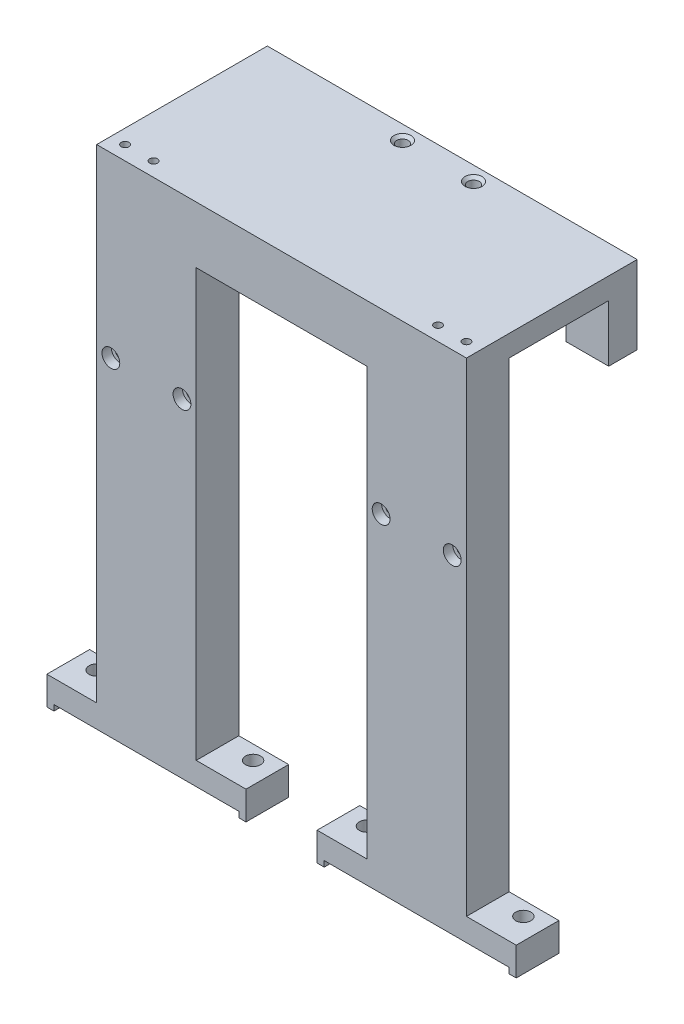
SolidWorks part; units mm, degrees
material "6061 Alloy"
ref_plane "Front Plane" through (0, 0, 0) normal (0, 0, 1) x (1, 0, 0)
ref_plane "Top Plane" through (0, 0, 0) normal (0, 1, 0) x (1, 0, 0)
ref_plane "Right Plane" through (0, 0, 0) normal (1, 0, 0) x (0, 0, -1)
sketch "Sketch1" plane through (0, 0, 0) normal (0, 0, 1) x (1, 0, 0)
  line L1 (-82.55, -114.3) -> (82.55, -114.3)
  line L2 (-82.55, -114.3) -> (-82.55, 114.3)
  line L3 (-82.55, 114.3) -> (82.55, 114.3)
  line L4 (82.55, -114.3) -> (82.55, 114.3)
  line L5 (-82.55, -114.3) -> (82.55, 114.3) construction
  line L6 (-82.55, 114.3) -> (82.55, -114.3) construction
  point P0 (0, 0)
  dimension "D1" = 228.6
  dimension "D2" = 165.1
extrude "Boss-Extrude1" add sketch "Sketch1" along normal blind 19.05
sketch "Sketch2" plane through (0, 0, 19.05) normal (0, 0, 1) x (1, 0, 0)
  line L0 (-82.55, -114.3) -> (82.55, -114.3) construction
  line L1 (-38.1, -114.3) -> (38.1, -114.3)
  line L2 (-38.1, -114.3) -> (-38.1, 88.9)
  line L3 (-38.1, 88.9) -> (38.1, 88.9)
  line L4 (38.1, -114.3) -> (38.1, 88.9)
  line L5 (-82.55, 114.3) -> (-82.55, -114.3) construction
  dimension "D1" = 203.2
  dimension "D2" = 76.2
  dimension "D3" = 44.45
extrude "Cut-Extrude1" cut sketch "Sketch2" against normal through all
sketch "Sketch3" plane through (0, 0, 0) normal (0, 0, -1) x (-1, 0, 0)
  line L0 (82.55, 114.3) -> (82.55, -114.3) construction
  line L1 (-82.55, 114.3) -> (82.55, 114.3)
  line L2 (-82.55, 114.3) -> (-82.55, 104.775)
  line L3 (-82.55, 104.775) -> (82.55, 104.775)
  line L4 (82.55, 114.3) -> (82.55, 104.775)
  dimension "D1" = 9.525
extrude "Boss-Extrude2" add sketch "Sketch3" along normal blind 57.15
sketch "Sketch4" plane through (0, 0, -57.15) normal (0, 0, -1) x (-1, 0, 0)
  line L7 (-82.55, 104.775) -> (-63.5, 104.775)
  line L8 (-82.55, 104.775) -> (-82.55, 79.375)
  line L9 (-82.55, 79.375) -> (-63.5, 79.375)
  line L10 (-63.5, 104.775) -> (-63.5, 79.375)
  dimension "D1" = 25.4
  dimension "D2" = 19.05
extrude "Boss-Extrude3" add sketch "Sketch4" against normal blind 12.7
mirror "Mirror1" about plane through (0, 0, 0) normal (1, 0, 0) of "Boss-Extrude3"
sketch "Sketch7" plane through (0, 0, 19.05) normal (0, 0, 1) x (1, 0, 0)
  line L0 (-82.55, -114.3) -> (-38.1, -114.3) construction
  line L1 (-104.775, -101.6) -> (-15.875, -101.6)
  line L2 (-104.775, -101.6) -> (-104.775, -114.3)
  line L3 (-104.775, -114.3) -> (-15.875, -114.3)
  line L4 (-15.875, -101.6) -> (-15.875, -114.3)
  line L5 (-104.775, -101.6) -> (-15.875, -114.3) construction
  line L6 (-104.775, -114.3) -> (-15.875, -101.6) construction
  line L7 (-82.55, 114.3) -> (-82.55, -114.3) construction
  point P0 (-60.325, -107.95)
  dimension "D1" = 0
  dimension "D2" = 88.9
  dimension "D3" = 22.225
  dimension "D4" = 12.7
extrude "Boss-Extrude4" add sketch "Sketch7" against normal blind 19.05
sketch "Sketch8" plane through (0, -114.3, 0) normal (0, -1, 0) x (-1, 0, 0)
  line L0 (104.775, -19.05) -> (15.875, -19.05) construction
  line L1 (101.6, 0) -> (19.05, 0)
  line L2 (101.6, 0) -> (101.6, -19.05)
  line L3 (101.6, -19.05) -> (19.05, -19.05)
  line L4 (19.05, 0) -> (19.05, -19.05)
  line L5 (101.6, 0) -> (19.05, -19.05) construction
  line L6 (101.6, -19.05) -> (19.05, 0) construction
  line L8 (104.775, 0) -> (104.775, -19.05) construction
  line L9 (15.875, 0) -> (15.875, -19.05) construction
  point P0 (60.325, -9.525)
  dimension "D1" = 19.05
  dimension "D2" = 3.175
  dimension "D3" = 3.175
extrude "Cut-Extrude4" cut sketch "Sketch8" against normal blind 2.54
mirror "Mirror3" about plane through (0, 0, 0) normal (1, 0, 0) of "Cut-Extrude4", "Boss-Extrude4"
hole_wizard "#8-32 Tapped Hole1" positions "Sketch11" profile "Sketch10" tap size "#8-32" standard "ANSI Inch"
sketch "Sketch11" plane through (0, 114.3, 0) normal (0, 1, 0) x (1, 0, 0)
  line L0 (-82.55, 0) -> (-82.55, -19.05) construction
  line L1 (-82.55, -19.05) -> (-82.55, 57.15) construction
  line L2 (82.55, 0) -> (82.55, -19.05) construction
  line L3 (82.55, -19.05) -> (82.55, 57.15) construction
  line L4 (82.55, -19.05) -> (-82.55, -19.05) construction
  point P0 (-76.2, -12.7)
  point P2 (-63.5, -12.7)
  point P4 (63.5, -12.7)
  point P6 (76.2, -12.7)
  dimension "D1" = 6.35
  dimension "D2" = 19.05
  dimension "D3" = 6.35
  dimension "D4" = 19.05
  dimension "D5" = 6.35
  dimension "D6" = 6.35
  dimension "D7" = 6.35
  dimension "D8" = 6.35
cosmetic thread "Hole Thread1" parameters "D1"=3.048, "D2"=4.1656
cosmetic thread "Hole Thread2" parameters "D1"=3.048, "D2"=4.1656
cosmetic thread "Hole Thread3" parameters "D1"=3.048, "D2"=4.1656
cosmetic thread "Hole Thread4" parameters "D1"=3.048, "D2"=4.1656
sketch "Sketch10" plane through (-76.2, 114.3, 12.7) normal (1, 0, 0) x (0, 0, 1)
  line L0 (0, 0) -> (0, 13.7378)
  line L1 (0, 13.7378) -> (1.7272, 12.7)
  line L2 (1.7272, 12.7) -> (1.7272, 0)
  line L5 (1.7272, 0) -> (0, 0)
  line L10 (0, 13.7378) -> (-1.7272, 12.7) construction
  line L11 (0, -6.35) -> (0, 107.95) construction
  dimension "Tap Drill Dia." = 3.4544
  dimension "Tap Drill Depth" = 12.7
  dimension "Drill Angle" = 118
hole_wizard "1/4 Clearance Hole1" positions "Sketch12" profile "Sketch13" hole size "1/4" standard "ANSI Inch" end condition up to next
sketch "Sketch12" plane through (0, -101.6, 0) normal (0, 1, 0) x (1, 0, 0)
  line L0 (-104.775, 0) -> (-104.775, -19.05) construction
  line L1 (-82.55, 0) -> (-104.775, 0) construction
  line L2 (-15.875, 0) -> (-38.1, 0) construction
  line L3 (-15.875, 0) -> (-15.875, -19.05) construction
  line L4 (15.875, 0) -> (15.875, -19.05) construction
  line L5 (15.875, 0) -> (38.1, 0) construction
  line L6 (82.55, 0) -> (104.775, 0) construction
  line L7 (104.775, 0) -> (104.775, -19.05) construction
  point P0 (-95.25, -6.35)
  point P2 (-25.4, -6.35)
  point P4 (25.4, -6.35)
  point P6 (95.25, -6.35)
  dimension "D1" = 9.525
  dimension "D2" = 6.35
  dimension "D3" = 6.35
  dimension "D4" = 9.525
  dimension "D5" = 9.525
  dimension "D6" = 6.35
  dimension "D7" = 6.35
  dimension "D8" = 9.525
sketch "Sketch13" plane through (-95.25, -101.6, 6.35) normal (1, 0, 0) x (0, 0, 1)
  line L0 (0, 0) -> (0, 10.16)
  line L1 (0, 10.16) -> (3.3782, 10.16)
  line L2 (3.3782, 10.16) -> (3.3782, 0)
  line L5 (3.3782, 0) -> (0, 0)
  line L11 (0, -6.35) -> (0, 107.95) construction
  dimension "Thru Hole Dia." = 6.7564
  dimension "Thru Hole Depth" = 10.16
hole_wizard "CBORE for #8 Socket Head Cap Screw1" positions "Sketch18" profile "Sketch19" counterbore size "#8" standard "ANSI Inch" end condition up to next
sketch "Sketch18" plane through (0, 0, 19.05) normal (0, 0, 1) x (1, 0, 0)
  line L0 (-82.55, 114.3) -> (-82.55, -101.6) construction
  line L1 (-38.1, 88.9) -> (-38.1, -101.6) construction
  line L2 (38.1, -101.6) -> (38.1, 88.9) construction
  line L3 (82.55, -101.6) -> (82.55, 114.3) construction
  point P0 (-76.2, 34.925)
  point P2 (-44.45, 34.925)
  point P4 (44.45, 34.925)
  point P6 (76.2, 34.925)
  dimension "D1" = 6.35
  dimension "D2" = 6.35
  dimension "D3" = 6.35
  dimension "D4" = 6.35
  dimension "D5" = 136.525
  dimension "D6" = 136.525
  dimension "D7" = 136.525
  dimension "D8" = 136.525
sketch "Sketch19" plane through (-76.2, 34.925, 19.05) normal (1, 0, 0) x (0, -1, 0)
  line L0 (0, 0) -> (0, 19.05)
  line L1 (0, 19.05) -> (2.2479, 19.05)
  line L3 (2.2479, 19.05) -> (2.2479, 4.1656)
  line L4 (2.2479, 4.1656) -> (3.9687, 4.1656)
  line L5 (3.9687, 4.1656) -> (3.9687, 0)
  line L7 (3.9687, 0) -> (0, 0)
  line L11 (0, -6.35) -> (0, 107.95) construction
  dimension "Thru Hole Dia." = 4.4958
  dimension "Thru Hole Depth" = 19.05
  dimension "C'Bore Dia." = 7.9375
  dimension "C'Bore Depth" = 4.1656
hole_wizard "1/4-20 Tapped Hole1" positions "Sketch20" profile "Sketch21" tap size "1/4-20" standard "ANSI Inch" end condition through all
sketch "Sketch20" plane through (0, 114.3, 0) normal (0, 1, 0) x (1, 0, 0)
  line L0 (-82.55, -19.05) -> (-82.55, 57.15) construction
  line L1 (82.55, -19.05) -> (82.55, 57.15) construction
  line L2 (-82.55, 57.15) -> (82.55, 57.15) construction
  point P0 (15.875, 50.8)
  point P2 (-15.875, 50.8)
  dimension "D1" = 66.675
  dimension "D2" = 66.675
  dimension "D3" = 6.35
  dimension "D4" = 6.35
sketch "Sketch21" plane through (15.875, 114.3, -50.8) normal (1, 0, 0) x (0, 0, 1)
  line L0 (0, 0) -> (0, 228.6)
  line L1 (0, 228.6) -> (2.5527, 228.6)
  line L2 (2.5527, 228.6) -> (2.5527, 1.2573)
  line L3 (2.5527, 1.2573) -> (3.81, 0)
  line L5 (3.81, 0) -> (0, 0)
  line L6 (-2.5527, 1.2573) -> (-3.81, 0) construction
  line L11 (0, -6.35) -> (0, 107.95) construction
  dimension "Thru Tap Drill Dia." = 5.1054
  dimension "Thru Tap Drill Depth" = 228.6
  dimension "Near C'Sink Dia." = 7.62
  dimension "Near C'Sink Angle" = 90
cosmetic thread "Hole Thread5" parameters "D2"=6.35
cosmetic thread "Hole Thread6" parameters "D2"=6.35
